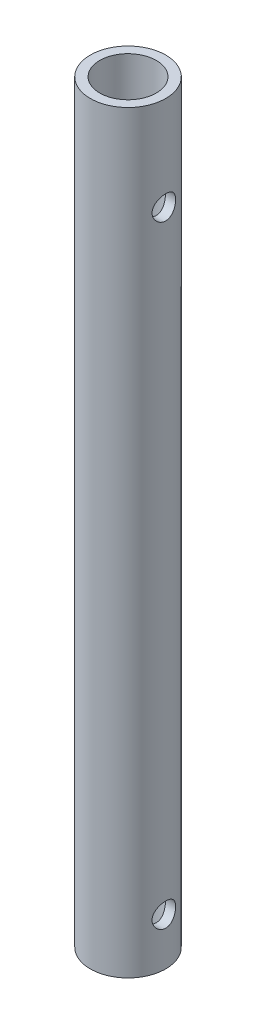
SolidWorks part; units mm, degrees
material "1060 Alloy"
ref_plane "Front" through (0, 0, 0) normal (0, 0, 1) x (1, 0, 0)
ref_plane "Top" through (0, 0, 0) normal (0, 1, 0) x (1, 0, 0)
ref_plane "Right" through (0, 0, 0) normal (1, 0, 0) x (0, 0, -1)
sketch "Sketch2" plane through (0, 0, 0) normal (1, 0, 0) x (0, 0, -1)
  line L14 (4, 0) -> (4, 80)
  line L15 (4, 80) -> (3, 80)
  line L16 (4, 0) -> (3, 0)
  line L17 (3, 80) -> (3, 0)
  line L18 (0, 0) -> (0, 50000) construction
  dimension "D1" = 8
  dimension "D2" = 6
  dimension "80" = 80
revolve "revolve 1" add sketch "Sketch2" angle 360 about L18
ref_axis "Axis1" through (0, 80, 0) along (0, -1, 0)
sketch "Sketch3" plane through (0, 0, 0) normal (1, 0, 0) x (0, 0, -1)
  line L0 (4, 80) -> (-4, 80) construction
  line L1 (-4, 0) -> (4, 0) construction
  circle A0 centre (0, 5) radius 1.25
  circle A1 centre (0, 70) radius 1.25
  dimension "D1" = 2.5
  dimension "D3" = 10
  dimension "D2" = 5
extrude "Cut-Extrude1" cut sketch "Sketch3" along normal through all both and the other way through all
